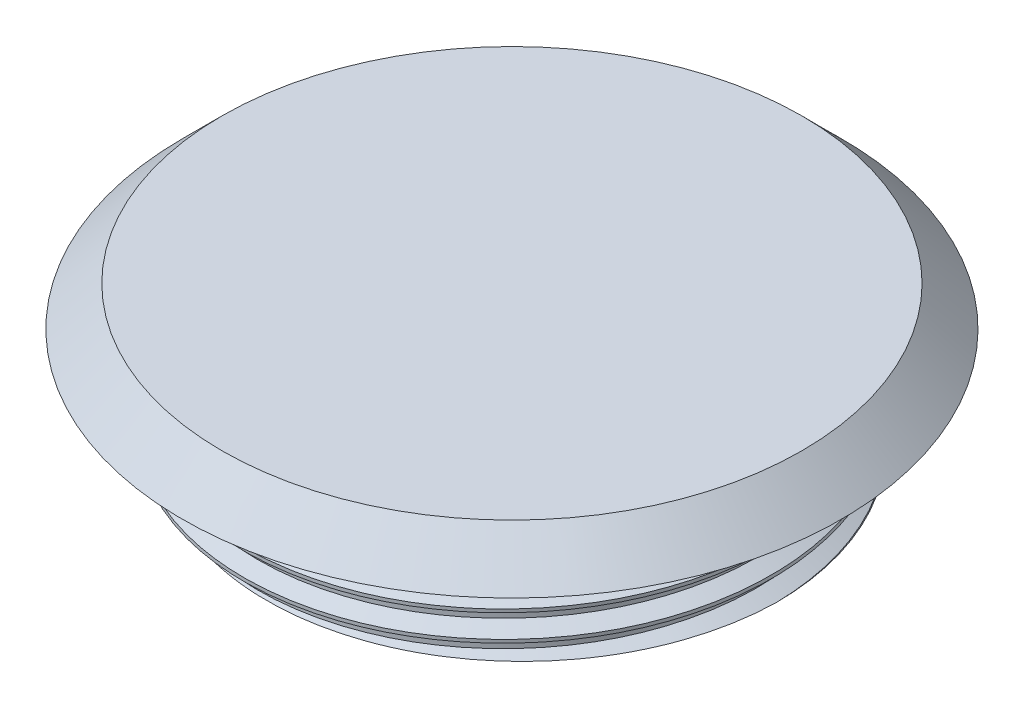
SolidWorks part; units mm, degrees
material "Простая углеродистая сталь"
ref_plane "Front" through (0, 0, 0) normal (0, 0, 1) x (1, 0, 0)
ref_plane "Top" through (0, 0, 0) normal (0, 1, 0) x (1, 0, 0)
ref_plane "Right" through (0, 0, 0) normal (1, 0, 0) x (0, 0, -1)
sketch "Эскиз1" plane through (0, 0, 0) normal (0, 0, 1) x (1, 0, 0)
  line L0 (0, 11) -> (0, 0) construction
  line L1 (0, 11) -> (-25, 11)
  line L2 (-25, 11) -> (-25, 8)
  line L3 (-25, 8) -> (-20, 8)
  line L4 (-20, 8) -> (-20, 0)
  line L5 (-20, 0) -> (0, 0)
  line L6 (0, 11) -> (0, 0)
  dimension "D1" = 40
  dimension "D2" = 8
  dimension "D3" = 5
  dimension "D4" = 3
revolve "Повернуть1" add sketch "Эскиз1" angle 360 about L0
chamfer "Фаска1" distance 3 angle 45 1 edges at (-25, 11, 0)
sketch "Эскиз2" plane through (0, 0, 0) normal (0, -1, 0) x (1, 0, 0)
  circle A0 centre (0, 0) radius 16
  circle A1 centre (0, 0) radius 20 construction
  dimension "D1" = 4
extrude "Вырез-Вытянуть1" cut sketch "Эскиз2" against normal up to surface (8 mm away) up to face at (-20, 8, 0)
chamfer "Фаска2" distance 3 angle 45 1 edges at (16, 8, 0)
thread "Резьба1" pitch 2 method cut profile "Профиль резьбы1" start angle 0, offset 4, length 10, pitch 2, diameter 40
ref_plane "Плоскость1" through (20, -4, 0) normal (0, 0, 1) x (1, 0, 0)
sketch "Профиль резьбы1" plane through (20, -4, 0) normal (0, 0, 1) x (1, 0, 0)
  line L0 (0, 0) -> (0, 2) construction
  line L11 (0, 0) -> (0, 1.75)
  line L12 (0, 1.75) -> (-1.0825, 1.125)
  line L13 (-1.0825, 1.125) -> (-1.0825, 0.625)
  line L15 (-1.0825, 0.625) -> (0, 0)
  line L17 (-1.0825, 0.875) -> (0, 0.875) construction
  point P2 (0, 0)
  dimension "Pitch" = 2
  dimension "Profile_Angle" = 60
  dimension "Profile_Land" = 0.5
  dimension "Profile_Height" = 1.0825
other "Переместить грань1" flip direction yes face at (13, 8, 0) offset 2 parameters "D1"=2
sketch "Эскиз3" plane through (0, 10, 0) normal (0, -1, 0) x (1, 0, 0)
  line L0 (0, 0) -> (-6.0121, 0) construction
  line L1 (11.3651, 5.5) -> (-11.3651, 5.5)
  line L2 (11.3651, 5.5) -> (11.3651, 12.5)
  line L3 (11.3651, 12.5) -> (-11.3651, 12.5)
  line L4 (-11.3651, 5.5) -> (-11.3651, 12.5)
  line L5 (0, 12.5) -> (0, 5.5) construction
  line L6 (11.3651, 9) -> (-11.3651, 9) construction
  line L7 (11.3651, -9) -> (-11.3651, -9) construction
  line L8 (0, -12.5) -> (0, -5.5) construction
  line L9 (-11.3651, -5.5) -> (-11.3651, -12.5)
  line L10 (11.3651, -12.5) -> (-11.3651, -12.5)
  line L11 (11.3651, -5.5) -> (11.3651, -12.5)
  line L12 (11.3651, -5.5) -> (-11.3651, -5.5)
  point P0 (0, 9)
  point P16 (0, -9)
  dimension "D1" = 11
  dimension "D2" = 7
extrude "Бобышка-Вытянуть1" add sketch "Эскиз3" along normal blind 1.5
sketch "Эскиз4" plane through (0, 10, 0) normal (0, -1, 0) x (1, 0, 0)
  line L0 (0, 0) -> (0, 7.3981) construction
  line L1 (-9.5263, 5.5) -> (9.5263, 5.5) construction
  line L2 (-7.5, -5.5) -> (-13.2951, -5.5)
  line L3 (-7.5, -5.5) -> (-7.5, 5.5)
  line L4 (-7.5, 5.5) -> (-13.2951, 5.5)
  line L5 (-13.2951, -5.5) -> (-13.2951, 5.5)
  line L6 (-10.3975, 5.5) -> (-10.3975, -5.5) construction
  line L7 (-7.5, 0) -> (-13.2951, 0) construction
  line L8 (7.5, 0) -> (13.2951, 0) construction
  line L9 (10.3975, 5.5) -> (10.3975, -5.5) construction
  line L10 (13.2951, -5.5) -> (13.2951, 5.5)
  line L11 (7.5, 5.5) -> (13.2951, 5.5)
  line L12 (7.5, -5.5) -> (7.5, 5.5)
  line L13 (7.5, -5.5) -> (13.2951, -5.5)
  point P3 (-10.3975, 0)
  point P7 (-5.5692, 5.5)
  point P18 (10.3975, 0)
  point P19 (-11.225, -5.5)
  dimension "D1" = 15
extrude "Бобышка-Вытянуть2" add sketch "Эскиз4" along normal up to surface (1.5 mm away) up to face at (0, 8.5, 9)
